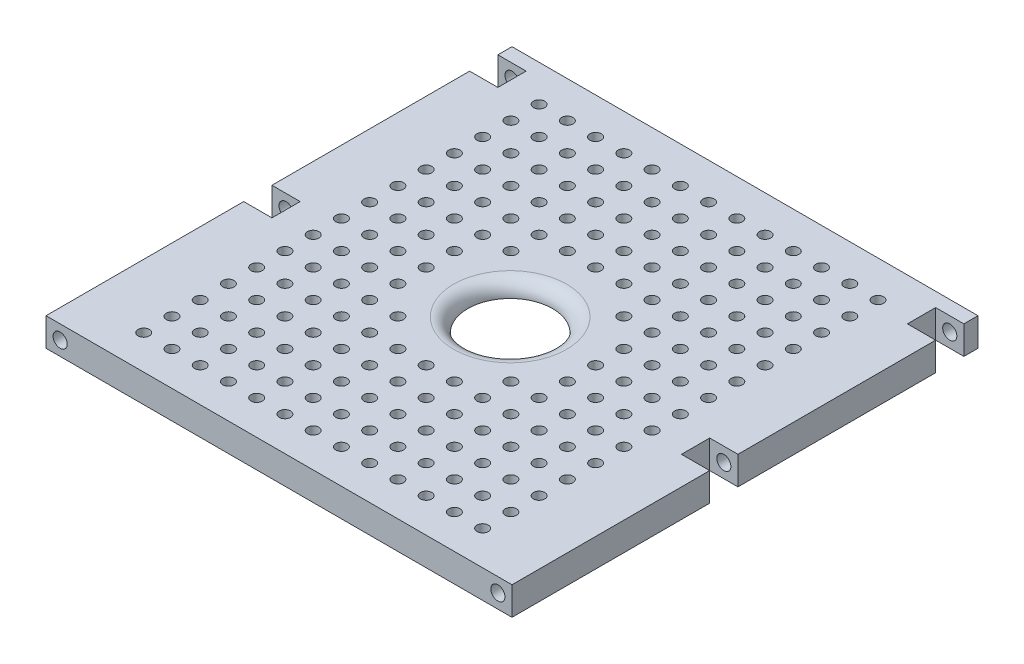
SolidWorks part; units mm, degrees
ref_plane "Plan de face" through (0, 0, 0) normal (0, 0, 1) x (1, 0, 0)
ref_plane "Plan de dessus" through (0, 0, 0) normal (0, 1, 0) x (1, 0, 0)
ref_plane "Plan de droite" through (0, 0, 0) normal (1, 0, 0) x (0, 0, -1)
sketch "Esquisse1" plane through (0, 0, 0) normal (0, 1, 0) x (1, 0, 0)
  line L0 (-82.5, 77.5) -> (-72.5, 77.5)
  line L1 (82.5, 82.5) -> (-82.5, 82.5)
  line L2 (82.5, 82.5) -> (82.5, 77.5)
  line L3 (82.5, -82.5) -> (-82.5, -82.5)
  line L4 (-82.5, 82.5) -> (-82.5, 77.5)
  line L5 (82.5, 82.5) -> (-82.5, -82.5) construction
  line L6 (82.5, -82.5) -> (-82.5, 82.5) construction
  line L7 (-72.5, 77.5) -> (-72.5, 67.5)
  line L8 (-72.5, 67.5) -> (-82.5, 67.5)
  line L9 (-82.5, -2.5) -> (-72.5, -2.5)
  line L10 (-72.5, -2.5) -> (-72.5, -12.5)
  line L11 (-72.5, -12.5) -> (-82.5, -12.5)
  line L12 (-82.5, -2.5) -> (-72.5, -12.5) construction
  line L13 (-72.5, -12.5) -> (-72.5448, -12.5817) construction
  line L14 (-82.5, 67.5) -> (-82.5, -2.5)
  line L15 (-82.5, -12.5) -> (-82.5, -82.5)
  line L16 (0, 16.0212) -> (0, -17.3175) construction
  line L17 (72.5, -12.5) -> (82.5, -12.5)
  line L18 (72.5, -2.5) -> (72.5, -12.5)
  line L19 (82.5, -2.5) -> (72.5, -2.5)
  line L20 (72.5, 77.5) -> (72.5, 67.5)
  line L21 (82.5, 77.5) -> (72.5, 77.5)
  line L22 (72.5, 67.5) -> (82.5, 67.5)
  line L23 (82.5, 67.5) -> (82.5, -2.5)
  line L24 (82.5, -12.5) -> (82.5, -82.5)
  circle A0 centre (0, -0.6481) radius 15
  point P0 (0, 0)
  point P12 (-77.5, -7.5)
  dimension "D9" = 30
  dimension "D1" = 165
  dimension "D2" = 165
  dimension "D3" = 5
  dimension "D4" = 10
  dimension "D5" = 10
  dimension "D6" = 10
  dimension "D7" = 10
  dimension "D8" = 90
extrude "BASE" add sketch "Esquisse1" along normal blind 10
sketch "Esquisse2" plane through (0, 0, -82.5) normal (0, 0, -1) x (-1, 0, 0)
  line L0 (-82.5, 5) -> (82.5, 5) construction
  line L1 (-82.5, 10) -> (-82.5, 0) construction
  line L2 (82.5, 10) -> (82.5, 0) construction
  line L3 (0, 17.3114) -> (0, -7.8072) construction
  circle A0 centre (-77.5, 5) radius 2.5
  circle A1 centre (77.5, 5) radius 2.5
  dimension "D1" = 5
  dimension "D2" = 5
extrude "VIDE VIS" cut sketch "Esquisse2" against normal through all
fillet "CONGE CABLE" radius 5 2 edges at (0, 0, 15.6481) (0, 10, 15.6481)
sketch "Esquisse3" plane through (0, 10, 0) normal (0, 1, 0) x (1, 0, 0)
  line L5 (62.5, -72.5) -> (-62.5, 72.5) construction
  line L6 (62.5, 72.5) -> (-62.5, -72.5) construction
  circle A0 centre (-60, 69.6) radius 2
  circle A1 centre (-50, 69.6) radius 2
  circle A2 centre (-40, 69.6) radius 2
  circle A3 centre (-30, 69.6) radius 2
  circle A4 centre (-20, 69.6) radius 2
  circle A5 centre (-10, 69.6) radius 2
  circle A6 centre (0, 69.6) radius 2
  circle A7 centre (10, 69.6) radius 2
  circle A8 centre (20, 69.6) radius 2
  circle A9 centre (30, 69.6) radius 2
  circle A10 centre (40, 69.6) radius 2
  circle A11 centre (50, 69.6) radius 2
  circle A12 centre (60, 69.6) radius 2
  circle A13 centre (-50, 59.6) radius 2
  circle A14 centre (-40, 59.6) radius 2
  circle A15 centre (-30, 59.6) radius 2
  circle A16 centre (-20, 59.6) radius 2
  circle A17 centre (-10, 59.6) radius 2
  circle A18 centre (0, 59.6) radius 2
  circle A19 centre (10, 59.6) radius 2
  circle A20 centre (20, 59.6) radius 2
  circle A21 centre (30, 59.6) radius 2
  circle A22 centre (40, 59.6) radius 2
  circle A23 centre (50, 59.6) radius 2
  circle A24 centre (60, 59.6) radius 2
  circle A25 centre (-50, 49.6) radius 2
  circle A26 centre (-40, 49.6) radius 2
  circle A27 centre (-30, 49.6) radius 2
  circle A28 centre (-20, 49.6) radius 2
  circle A29 centre (-10, 49.6) radius 2
  circle A30 centre (0, 49.6) radius 2
  circle A31 centre (10, 49.6) radius 2
  circle A32 centre (20, 49.6) radius 2
  circle A33 centre (30, 49.6) radius 2
  circle A34 centre (40, 49.6) radius 2
  circle A35 centre (50, 49.6) radius 2
  circle A36 centre (60, 49.6) radius 2
  circle A37 centre (-50, 39.6) radius 2
  circle A38 centre (-40, 39.6) radius 2
  circle A39 centre (-30, 39.6) radius 2
  circle A40 centre (-20, 39.6) radius 2
  circle A41 centre (-10, 39.6) radius 2
  circle A42 centre (0, 39.6) radius 2
  circle A43 centre (10, 39.6) radius 2
  circle A44 centre (20, 39.6) radius 2
  circle A45 centre (30, 39.6) radius 2
  circle A46 centre (40, 39.6) radius 2
  circle A47 centre (50, 39.6) radius 2
  circle A48 centre (60, 39.6) radius 2
  circle A49 centre (-50, 29.6) radius 2
  circle A50 centre (-40, 29.6) radius 2
  circle A51 centre (-30, 29.6) radius 2
  circle A52 centre (-20, 29.6) radius 2
  circle A53 centre (-10, 29.6) radius 2
  circle A54 centre (0, 29.6) radius 2
  circle A55 centre (10, 29.6) radius 2
  circle A56 centre (20, 29.6) radius 2
  circle A57 centre (30, 29.6) radius 2
  circle A58 centre (40, 29.6) radius 2
  circle A59 centre (50, 29.6) radius 2
  circle A60 centre (60, 29.6) radius 2
  circle A61 centre (-50, 19.6) radius 2
  circle A62 centre (-40, 19.6) radius 2
  circle A63 centre (-30, 19.6) radius 2
  circle A64 centre (-20, 19.6) radius 2
  circle A68 centre (20, 19.6) radius 2
  circle A69 centre (30, 19.6) radius 2
  circle A70 centre (40, 19.6) radius 2
  circle A71 centre (50, 19.6) radius 2
  circle A72 centre (60, 19.6) radius 2
  circle A73 centre (-50, 9.6) radius 2
  circle A74 centre (-40, 9.6) radius 2
  circle A75 centre (-30, 9.6) radius 2
  circle A81 centre (30, 9.6) radius 2
  circle A82 centre (40, 9.6) radius 2
  circle A83 centre (50, 9.6) radius 2
  circle A84 centre (60, 9.6) radius 2
  circle A85 centre (-50, -0.4) radius 2
  circle A86 centre (-40, -0.4) radius 2
  circle A87 centre (-30, -0.4) radius 2
  circle A93 centre (30, -0.4) radius 2
  circle A94 centre (40, -0.4) radius 2
  circle A95 centre (50, -0.4) radius 2
  circle A96 centre (60, -0.4) radius 2
  circle A97 centre (-50, -10.4) radius 2
  circle A98 centre (-40, -10.4) radius 2
  circle A99 centre (-30, -10.4) radius 2
  circle A105 centre (30, -10.4) radius 2
  circle A106 centre (40, -10.4) radius 2
  circle A107 centre (50, -10.4) radius 2
  circle A108 centre (60, -10.4) radius 2
  circle A109 centre (-50, -20.4) radius 2
  circle A110 centre (-40, -20.4) radius 2
  circle A111 centre (-30, -20.4) radius 2
  circle A112 centre (-20, -20.4) radius 2
  circle A116 centre (20, -20.4) radius 2
  circle A117 centre (30, -20.4) radius 2
  circle A118 centre (40, -20.4) radius 2
  circle A119 centre (50, -20.4) radius 2
  circle A120 centre (60, -20.4) radius 2
  circle A121 centre (-50, -30.4) radius 2
  circle A122 centre (-40, -30.4) radius 2
  circle A123 centre (-30, -30.4) radius 2
  circle A124 centre (-20, -30.4) radius 2
  circle A125 centre (-10, -30.4) radius 2
  circle A126 centre (0, -30.4) radius 2
  circle A127 centre (10, -30.4) radius 2
  circle A128 centre (20, -30.4) radius 2
  circle A129 centre (30, -30.4) radius 2
  circle A130 centre (40, -30.4) radius 2
  circle A131 centre (50, -30.4) radius 2
  circle A132 centre (60, -30.4) radius 2
  circle A133 centre (-50, -40.4) radius 2
  circle A134 centre (-40, -40.4) radius 2
  circle A135 centre (-30, -40.4) radius 2
  circle A136 centre (-20, -40.4) radius 2
  circle A137 centre (-10, -40.4) radius 2
  circle A138 centre (0, -40.4) radius 2
  circle A139 centre (10, -40.4) radius 2
  circle A140 centre (20, -40.4) radius 2
  circle A141 centre (30, -40.4) radius 2
  circle A142 centre (40, -40.4) radius 2
  circle A143 centre (50, -40.4) radius 2
  circle A144 centre (60, -40.4) radius 2
  circle A145 centre (-50, -50.4) radius 2
  circle A146 centre (-40, -50.4) radius 2
  circle A147 centre (-30, -50.4) radius 2
  circle A148 centre (-20, -50.4) radius 2
  circle A149 centre (-10, -50.4) radius 2
  circle A150 centre (0, -50.4) radius 2
  circle A151 centre (10, -50.4) radius 2
  circle A152 centre (20, -50.4) radius 2
  circle A153 centre (30, -50.4) radius 2
  circle A154 centre (40, -50.4) radius 2
  circle A155 centre (50, -50.4) radius 2
  circle A156 centre (60, -50.4) radius 2
  circle A157 centre (-50, -60.4) radius 2
  circle A158 centre (-40, -60.4) radius 2
  circle A159 centre (-30, -60.4) radius 2
  circle A160 centre (-20, -60.4) radius 2
  circle A161 centre (-10, -60.4) radius 2
  circle A162 centre (0, -60.4) radius 2
  circle A163 centre (10, -60.4) radius 2
  circle A164 centre (20, -60.4) radius 2
  circle A165 centre (30, -60.4) radius 2
  circle A166 centre (40, -60.4) radius 2
  circle A167 centre (50, -60.4) radius 2
  circle A168 centre (60, -60.4) radius 2
  circle A169 centre (-50, -70.4) radius 2
  circle A170 centre (-40, -70.4) radius 2
  circle A171 centre (-30, -70.4) radius 2
  circle A172 centre (-20, -70.4) radius 2
  circle A173 centre (-10, -70.4) radius 2
  circle A174 centre (0, -70.4) radius 2
  circle A175 centre (10, -70.4) radius 2
  circle A176 centre (20, -70.4) radius 2
  circle A177 centre (30, -70.4) radius 2
  circle A178 centre (40, -70.4) radius 2
  circle A179 centre (50, -70.4) radius 2
  circle A180 centre (60, -70.4) radius 2
  circle A181 centre (-60, 59.6) radius 2
  circle A182 centre (-60, 49.6) radius 2
  circle A183 centre (-60, 39.6) radius 2
  circle A184 centre (-60, 29.6) radius 2
  circle A185 centre (-60, 19.6) radius 2
  circle A186 centre (-60, 9.6) radius 2
  circle A187 centre (-60, -0.4) radius 2
  circle A188 centre (-60, -10.4) radius 2
  circle A189 centre (-60, -20.4) radius 2
  circle A190 centre (-60, -30.4) radius 2
  circle A191 centre (-60, -40.4) radius 2
  circle A192 centre (-60, -50.4) radius 2
  circle A193 centre (-60, -60.4) radius 2
  circle A194 centre (-60, -70.4) radius 2
  circle A195 centre (0, 19.6) radius 2 [skipped]
  circle A196 centre (-10, 9.6) radius 2 [skipped]
  circle A197 centre (0, 9.6) radius 2 [skipped]
  circle A198 centre (10, 9.6) radius 2 [skipped]
  circle A199 centre (10, -0.4) radius 2 [skipped]
  circle A200 centre (10, -10.4) radius 2 [skipped]
  circle A201 centre (0, -0.4) radius 2 [skipped]
  circle A202 centre (-10, -0.4) radius 2 [skipped]
  circle A203 centre (0, -10.4) radius 2 [skipped]
  circle A204 centre (-10, -10.4) radius 2 [skipped]
  circle A205 centre (20, -0.4) radius 2 [skipped]
  circle A206 centre (20, -10.4) radius 2 [skipped]
  circle A207 centre (10, -20.4) radius 2 [skipped]
  circle A208 centre (0, -20.4) radius 2 [skipped]
  circle A209 centre (-10, -20.4) radius 2 [skipped]
  circle A210 centre (-20, -0.4) radius 2 [skipped]
  circle A211 centre (-20, 9.6) radius 2 [skipped]
  circle A212 centre (-20, -10.4) radius 2 [skipped]
  circle A213 centre (20, 9.6) radius 2 [skipped]
  circle A214 centre (-10, 19.6) radius 2 [skipped]
  circle A215 centre (10, 19.6) radius 2 [skipped]
  point P0 (0, 0)
  point P10 (-60, 69.6)
  dimension "D3" = 4
  dimension "D1" = 2.5
  dimension "D5" = 13
  dimension "D6" = 15
extrude "VIDE TROU" cut sketch "Esquisse3" against normal through all
sketch "Esquisse4" plane through (0, 0, 0) normal (0, -1, 0) x (1, 0, 0)
  line L0 (82.5, 2.5) -> (82.5, -67.5) construction
  line L1 (-64.5, 74.5) -> (64.5, 74.5)
  line L2 (-64.5, 74.5) -> (-64.5, -73.2038)
  line L3 (-64.5, -73.2038) -> (64.5, -73.2038)
  line L4 (64.5, 74.5) -> (64.5, -73.2038)
  line L5 (-64.5, 74.5) -> (64.5, -73.2038) construction
  line L6 (-64.5, -73.2038) -> (64.5, 74.5) construction
  line L7 (-82.5, 82.5) -> (82.5, 82.5) construction
  point P0 (0, 0.6481)
  dimension "D1" = 18
  dimension "D2" = 8
extrude "VIDE 1/2" cut sketch "Esquisse4" against normal blind 5
